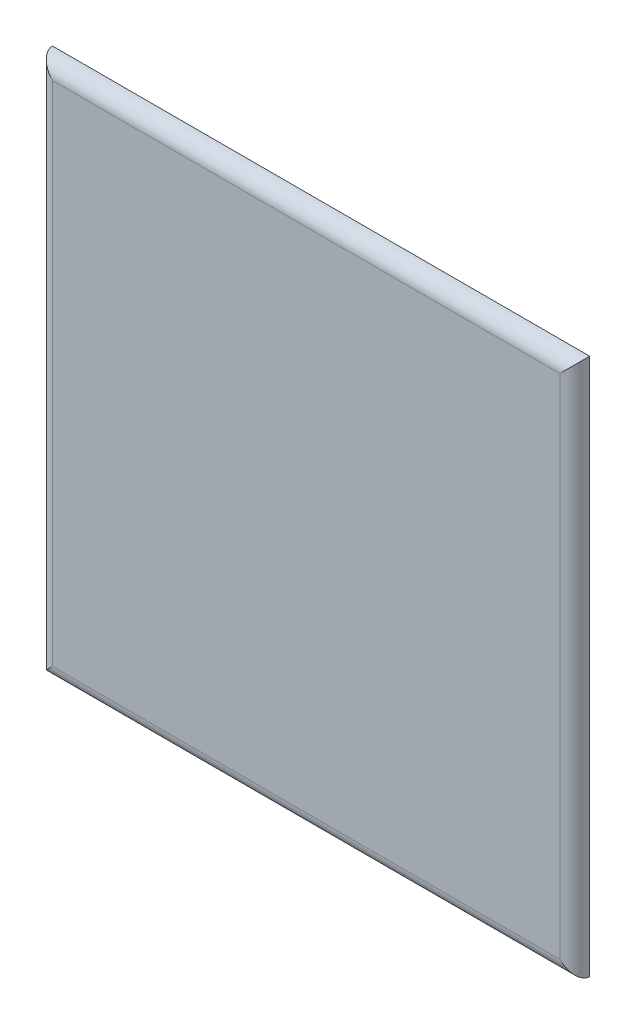
SolidWorks part; units mm, degrees
material "PS HI"
ref_plane "Ön Düzlem" through (0, 0, 0) normal (0, 0, 1) x (1, 0, 0)
ref_plane "Üst Düzlem" through (0, 0, 0) normal (0, 1, 0) x (1, 0, 0)
ref_plane "Sağ Düzlem" through (0, 0, 0) normal (1, 0, 0) x (0, 0, -1)
sketch "Çizim1" plane through (0, 0, 0) normal (0, 0, 1) x (1, 0, 0)
  line L1 (-9, -9) -> (9, -9)
  line L2 (-9, -9) -> (-9, 9)
  line L3 (-9, 9) -> (9, 9)
  line L4 (9, -9) -> (9, 9)
  line L5 (-9, -9) -> (9, 9) construction
  line L6 (-9, 9) -> (9, -9) construction
  point P0 (0, 0)
  dimension "D1" = 18
  dimension "D2" = 18
extrude "Yükseklik-Ekstrüzyon1" add sketch "Çizim1" along normal mid plane 0.5
fillet "Radyus1" radius 0.5 4 edges at (0, 9, 0.25) (9, 0, 0.25) (0, -9, 0.25) (-9, 0, 0.25)
